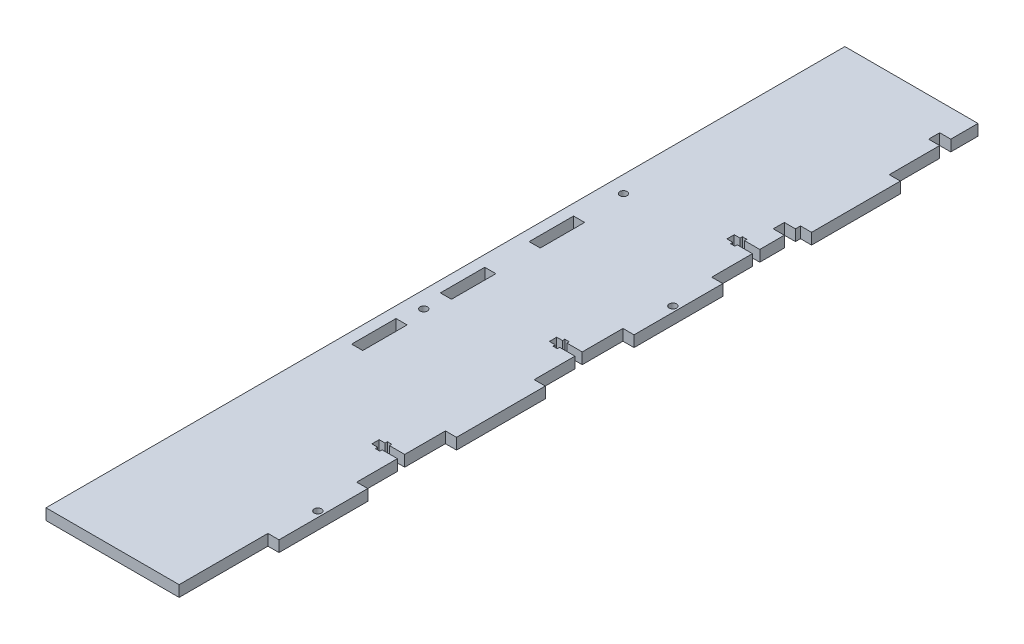
SolidWorks part; units mm, degrees
ref_plane "Front Plane" through (0, 0, 0) normal (0, 0, 1) x (1, 0, 0)
ref_plane "Top Plane" through (0, 0, 0) normal (0, 1, 0) x (1, 0, 0)
ref_plane "Right Plane" through (0, 0, 0) normal (1, 0, 0) x (0, 0, -1)
sketch "Sketch1" plane through (0, 0, 0) normal (0, 0, 1) x (1, 0, 0)
  line L1 (-38.1, -38.1) -> (38.1, -38.1) construction
  line L2 (-38.1, -38.1) -> (-38.1, 38.1) construction
  line L3 (-38.1, 38.1) -> (38.1, 38.1) construction
  line L4 (38.1, -38.1) -> (38.1, 38.1) construction
  line L5 (-38.1, -38.1) -> (38.1, 38.1) construction
  line L6 (-38.1, 38.1) -> (38.1, -38.1) construction
  line L7 (-38.1, -38.1) -> (38.1, -38.1)
  line L8 (-38.1, -38.1) -> (-38.1, -44.45)
  line L9 (-38.1, -44.45) -> (38.1, -44.45)
  line L10 (38.1, -38.1) -> (38.1, -44.45)
  point P0 (0, 0)
  dimension "D1" = 76.2
  dimension "D2" = 6.35
extrude "Boss-Extrude1" add sketch "Sketch1" along normal blind 457.2
sketch "Sketch2" plane through (38.1, 0, 0) normal (1, 0, 0) x (0, 0, -1)
  line L0 (-457.2, -44.45) -> (0, -44.45) construction
  line L1 (-406.4, -44.45) -> (-355.6, -44.45)
  line L2 (-406.4, -44.45) -> (-406.4, -38.1)
  line L3 (-406.4, -38.1) -> (-355.6, -38.1)
  line L4 (-355.6, -44.45) -> (-355.6, -38.1)
  line L5 (-406.4, -44.45) -> (-406.4, -38.1) construction
  line L6 (-355.6, -38.1) -> (-355.6, -44.45) construction
  line L7 (-457.2, -38.1) -> (0, -38.1) construction
  line L8 (-304.8, -44.45) -> (-304.8, -38.1) construction
  line L9 (-304.8, -44.45) -> (-254, -44.45)
  line L10 (-304.8, -44.45) -> (-304.8, -38.1)
  line L11 (-304.8, -38.1) -> (-254, -38.1)
  line L12 (-254, -44.45) -> (-254, -38.1)
  line L13 (-203.2, -44.45) -> (-152.4, -44.45)
  line L14 (-203.2, -44.45) -> (-203.2, -38.1)
  line L15 (-203.2, -38.1) -> (-152.4, -38.1)
  line L16 (-152.4, -44.45) -> (-152.4, -38.1)
  line L17 (-101.6, -44.45) -> (-50.8, -44.45)
  line L18 (-101.6, -44.45) -> (-101.6, -38.1)
  line L19 (-101.6, -38.1) -> (-50.8, -38.1)
  line L20 (-50.8, -44.45) -> (-50.8, -38.1)
  line L21 (-254, -38.1) -> (-254, -44.45) construction
  line L22 (-203.2, -44.45) -> (-203.2, -38.1) construction
  line L23 (-152.4, -38.1) -> (-152.4, -44.45) construction
  line L24 (-101.6, -44.45) -> (-101.6, -38.1) construction
  line L25 (-50.8, -38.1) -> (-50.8, -44.45) construction
extrude "Boss-Extrude2" add sketch "Sketch2" along normal up to surface (6.35 mm away) up to face at (38.1, -41.275, 228.6)
sketch "Sketch3" plane through (0, -38.1, 0) normal (0, 1, 0) x (1, 0, 0)
  line L0 (38.1, -152.4) -> (38.1, -101.6) construction
  line L1 (31.75, -104.4875) -> (38.1, -104.4875)
  line L2 (31.75, -104.4875) -> (31.75, -110.8375)
  line L3 (31.75, -110.8375) -> (38.1, -110.8375)
  line L4 (38.1, -104.4875) -> (38.1, -110.8375)
extrude "Cut-Extrude1" cut sketch "Sketch3" against normal blind 6.35
sketch "Sketch4" plane through (0, -38.1, 0) normal (0, 1, 0) x (1, 0, 0)
  line L0 (38.1, -50.8) -> (38.1, 0) construction
  line L1 (31.75, -21.9375) -> (38.1, -21.9375)
  line L2 (31.75, -21.9375) -> (31.75, -15.5875)
  line L3 (31.75, -15.5875) -> (38.1, -15.5875)
  line L4 (38.1, -21.9375) -> (38.1, -15.5875)
extrude "Cut-Extrude2" cut sketch "Sketch4" against normal through all
sketch "Sketch5" plane through (0, -38.1, 0) normal (0, 1, 0) x (1, 0, 0)
  line L1 (-25.4, -288.6375) -> (-31.75, -288.6375)
  line L2 (-25.4, -288.6375) -> (-25.4, -263.2375)
  line L3 (-25.4, -263.2375) -> (-31.75, -263.2375)
  line L4 (-31.75, -288.6375) -> (-31.75, -263.2375)
  line L5 (-25.4, -237.8375) -> (-31.75, -237.8375)
  line L6 (-25.4, -237.8375) -> (-25.4, -212.4375)
  line L7 (-25.4, -212.4375) -> (-31.75, -212.4375)
  line L8 (-31.75, -237.8375) -> (-31.75, -212.4375)
  line L9 (-25.4, -187.0375) -> (-31.75, -187.0375)
  line L10 (-25.4, -187.0375) -> (-25.4, -161.6375)
  line L11 (-25.4, -161.6375) -> (-31.75, -161.6375)
  line L12 (-31.75, -187.0375) -> (-31.75, -161.6375)
extrude "Cut-Extrude3" cut sketch "Sketch5" against normal through all
sketch "Sketch6" plane through (0, -44.45, 0) normal (0, -1, 0) x (-1, 0, 0)
  line L0 (31.75, -252.633) -> (25.4, -248.442) construction
  line L1 (31.75, -138.333) -> (25.4, -134.142) construction
  circle A0 centre (28.575, -250.5375) radius 2.0955
  circle A1 centre (28.575, -136.2375) radius 2.0955
  dimension "D1" = 4.191
extrude "Cut-Extrude4" cut sketch "Sketch6" against normal through all
sketch "Sketch7" plane through (0, -38.1, 0) normal (0, 1, 0) x (1, 0, 0)
  line L0 (44.45, -378.9045) -> (38.1, -383.0955) construction
  line L1 (44.45, -406.4) -> (44.45, -355.6) construction
  line L2 (38.1, -378.9045) -> (44.45, -378.9045) construction
  line L3 (44.45, -383.0955) -> (38.1, -378.9045) construction
  line L4 (38.1, -383.0955) -> (44.45, -383.0955) construction
  line L5 (44.45, -175.7045) -> (38.1, -179.8955) construction
  line L6 (44.45, -203.2) -> (44.45, -152.4) construction
  line L7 (38.1, -175.7045) -> (44.45, -175.7045) construction
  line L8 (38.1, -175.7045) -> (44.45, -179.8955) construction
  line L9 (38.1, -179.8955) -> (44.45, -179.8955) construction
  circle A0 centre (41.275, -381) radius 2.0955
  circle A1 centre (41.275, -177.8) radius 2.0955
  dimension "D1" = 4.191
extrude "Cut-Extrude5" cut sketch "Sketch7" against normal through all
sketch "Sketch8" plane through (0, -44.45, 0) normal (0, -1, 0) x (-1, 0, 0)
  line L2 (-38.1, -355.6) -> (-38.1, -304.8) construction
  line L3 (-44.45, -355.6) -> (-38.1, -355.6) construction
  line L4 (-44.45, -304.8) -> (-38.1, -304.8) construction
  line L10 (-38.1, -254) -> (-38.1, -203.2) construction
  line L11 (-44.45, -203.2) -> (-38.1, -203.2) construction
  line L12 (-38.1, -254) -> (-44.45, -254) construction
  line L13 (-38.1, -152.4) -> (-38.1, -110.8375) construction
  line L14 (-44.45, -101.6) -> (-38.1, -101.6) construction
  line L15 (-44.45, -152.4) -> (-38.1, -152.4) construction
  line B0 (-38.1, -328.1045) -> (-38.1, -332.2955)
  line B1 (-26.797, -332.2955) -> (-26.797, -333.629)
  line B2 (-26.797, -333.629) -> (-29.337, -333.629)
  line B3 (-29.337, -333.629) -> (-29.337, -332.2955)
  line B4 (-29.337, -332.2955) -> (-38.1, -332.2955)
  line B5 (-26.797, -332.2955) -> (-23.495, -332.2955)
  line B6 (-23.495, -332.2955) -> (-23.495, -328.1045)
  line B7 (-26.797, -328.1045) -> (-23.495, -328.1045)
  line B8 (-29.337, -328.1045) -> (-38.1, -328.1045)
  line B9 (-29.337, -326.771) -> (-29.337, -328.1045)
  line B10 (-26.797, -326.771) -> (-29.337, -326.771)
  line B11 (-26.797, -328.1045) -> (-26.797, -326.771)
  line B12 (-38.1, -330.2) -> (-23.495, -330.2) construction
  line B13 (-38.1, -226.5045) -> (-38.1, -230.6955)
  line B14 (-26.797, -230.6955) -> (-26.797, -232.029)
  line B15 (-26.797, -232.029) -> (-29.337, -232.029)
  line B16 (-29.337, -232.029) -> (-29.337, -230.6955)
  line B17 (-29.337, -230.6955) -> (-38.1, -230.6955)
  line B18 (-26.797, -230.6955) -> (-23.495, -230.6955)
  line B19 (-23.495, -230.6955) -> (-23.495, -226.5045)
  line B20 (-26.797, -226.5045) -> (-23.495, -226.5045)
  line B21 (-29.337, -226.5045) -> (-38.1, -226.5045)
  line B22 (-29.337, -225.171) -> (-29.337, -226.5045)
  line B23 (-26.797, -225.171) -> (-29.337, -225.171)
  line B24 (-26.797, -226.5045) -> (-26.797, -225.171)
  line B25 (-38.1, -228.6) -> (-23.495, -228.6) construction
  line B26 (-38.1, -124.9045) -> (-38.1, -129.0955)
  line B27 (-26.797, -129.0955) -> (-26.797, -130.429)
  line B28 (-26.797, -130.429) -> (-29.337, -130.429)
  line B29 (-29.337, -130.429) -> (-29.337, -129.0955)
  line B30 (-29.337, -129.0955) -> (-38.1, -129.0955)
  line B31 (-26.797, -129.0955) -> (-23.495, -129.0955)
  line B32 (-23.495, -129.0955) -> (-23.495, -124.9045)
  line B33 (-26.797, -124.9045) -> (-23.495, -124.9045)
  line B34 (-29.337, -124.9045) -> (-38.1, -124.9045)
  line B35 (-29.337, -123.571) -> (-29.337, -124.9045)
  line B36 (-26.797, -123.571) -> (-29.337, -123.571)
  line B37 (-26.797, -124.9045) -> (-26.797, -123.571)
  line B38 (-38.1, -127) -> (-23.495, -127) construction
sketch_block_instance "TSlot-1"
sketch_block "TSlot" parameters "D1"=3.302, "D2"=2.54, "D3"=3.175, "D4"=8.763, "D5"=1.3462
sketch_block_instance "TSlot-3"
sketch_block_instance "TSlot-4"
extrude "Cut-Extrude6" cut sketch "Sketch8" against normal through all
